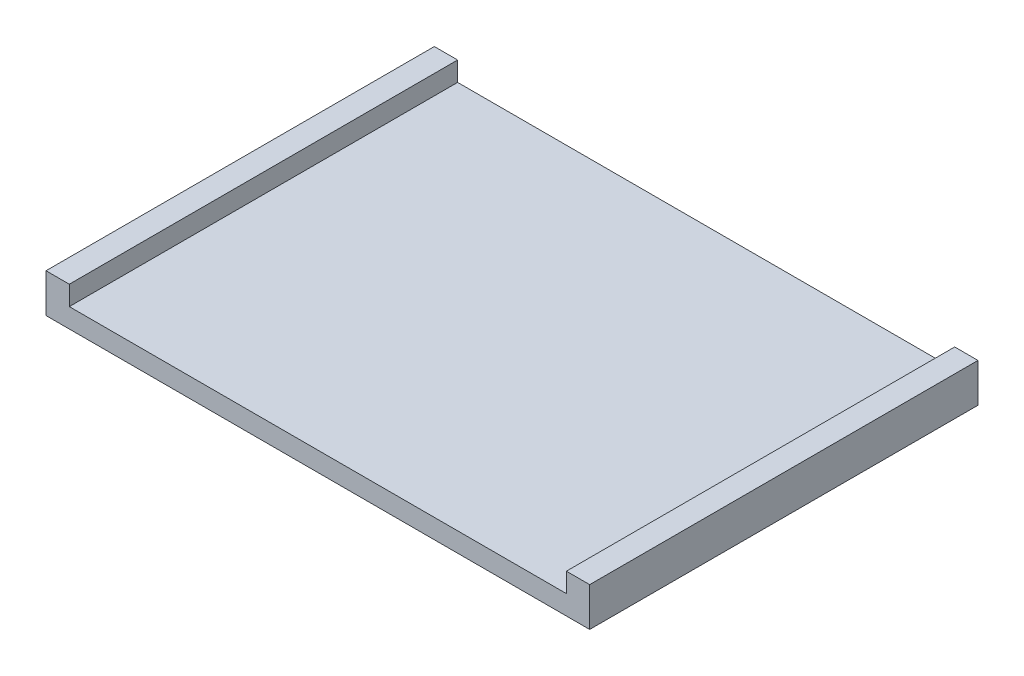
SolidWorks part; units mm, degrees
ref_plane "Plan de face" through (0, 0, 0) normal (0, 0, 1) x (1, 0, 0)
ref_plane "Plan de dessus" through (0, 0, 0) normal (0, 1, 0) x (1, 0, 0)
ref_plane "Plan de droite" through (0, 0, 0) normal (1, 0, 0) x (0, 0, -1)
sketch "Sketch1" plane through (0, 0, 0) normal (0, 1, 0) x (1, 0, 0)
  line L1 (-70, 50) -> (70, 50)
  line L2 (-70, 50) -> (-70, -50)
  line L3 (-70, -50) -> (70, -50)
  line L4 (70, 50) -> (70, -50)
  line L5 (-70, 50) -> (70, -50) construction
  line L6 (-70, -50) -> (70, 50) construction
  point P0 (0, 0)
  dimension "D1" = 140
  dimension "D2" = 100
extrude "Boss-Extrude1" add sketch "Sketch1" along normal blind 5
sketch "Sketch2" plane through (0, 5, 0) normal (0, 1, 0) x (1, 0, 0)
  line L0 (-70, -50) -> (70, -50) construction
  line L1 (-70, 50) -> (-64, 50)
  line L2 (-70, 50) -> (-70, -50)
  line L3 (-70, -50) -> (-64, -50)
  line L4 (-64, 50) -> (-64, -50)
  line L6 (70, 50) -> (64, 50)
  line L7 (70, 50) -> (70, -50)
  line L8 (70, -50) -> (64, -50)
  line L9 (64, 50) -> (64, -50)
  dimension "D1" = 128
extrude "Boss-Extrude2" add sketch "Sketch2" along normal blind 5
